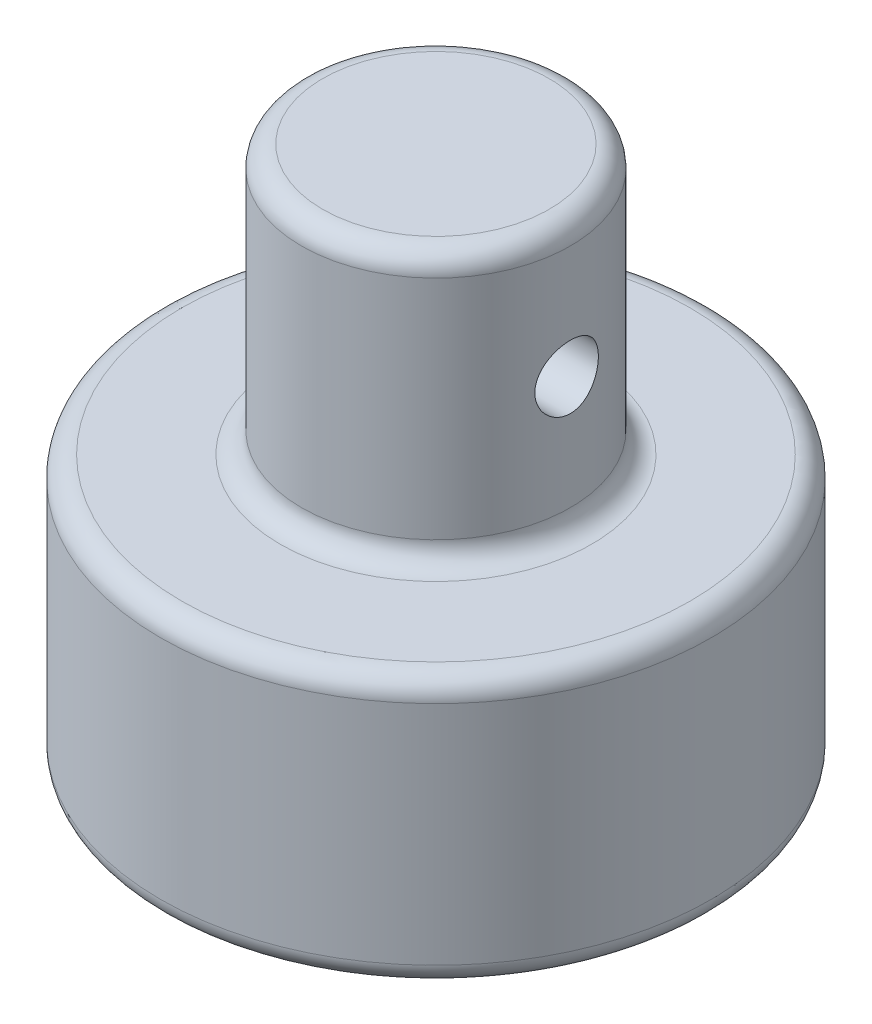
SolidWorks part; units mm, degrees
ref_plane "Front Plane" through (0, 0, 0) normal (0, 0, 1) x (1, 0, 0)
ref_plane "Top Plane" through (0, 0, 0) normal (0, 1, 0) x (1, 0, 0)
ref_plane "Right Plane" through (0, 0, 0) normal (1, 0, 0) x (0, 0, -1)
sketch "Sketch2" plane through (0, 0, 0) normal (0, 1, 0) x (1, 0, 0)
  circle A0 centre (0, 0) radius 6.5
  dimension "D1" = 13
extrude "Boss-Extrude1" add sketch "Sketch2" along normal blind 6.35
sketch "Sketch3" plane through (0, 6.35, 0) normal (0, 1, 0) x (1, 0, 0)
  circle A0 centre (0, 0) radius 3.175
  dimension "D1" = 6.35
extrude "Boss-Extrude2" add sketch "Sketch3" along normal blind 6.35 contours A0
sketch "Sketch4" plane through (0, 0, 0) normal (1, 0, 0) x (0, 0, -1)
  line L0 (0, 13.4187) -> (0, 0) construction
  line L1 (3.175, 9.525) -> (-3.175, 9.525) construction
  line L2 (3.175, 6.35) -> (3.175, 12.7) construction
  line L3 (-3.175, 12.7) -> (-3.175, 6.35) construction
  circle A0 centre (0, 9.525) radius 0.75
  dimension "D1" = 1.5
extrude "Cut-Extrude1" cut sketch "Sketch4" against normal blind 6.35 and the other way blind 6.35
fillet "Fillet1" radius 0.5 4 edges at (0, 0, 6.5) (0, 12.7, 3.175) (0, 6.35, 6.5) (0, 6.35, 3.175)
